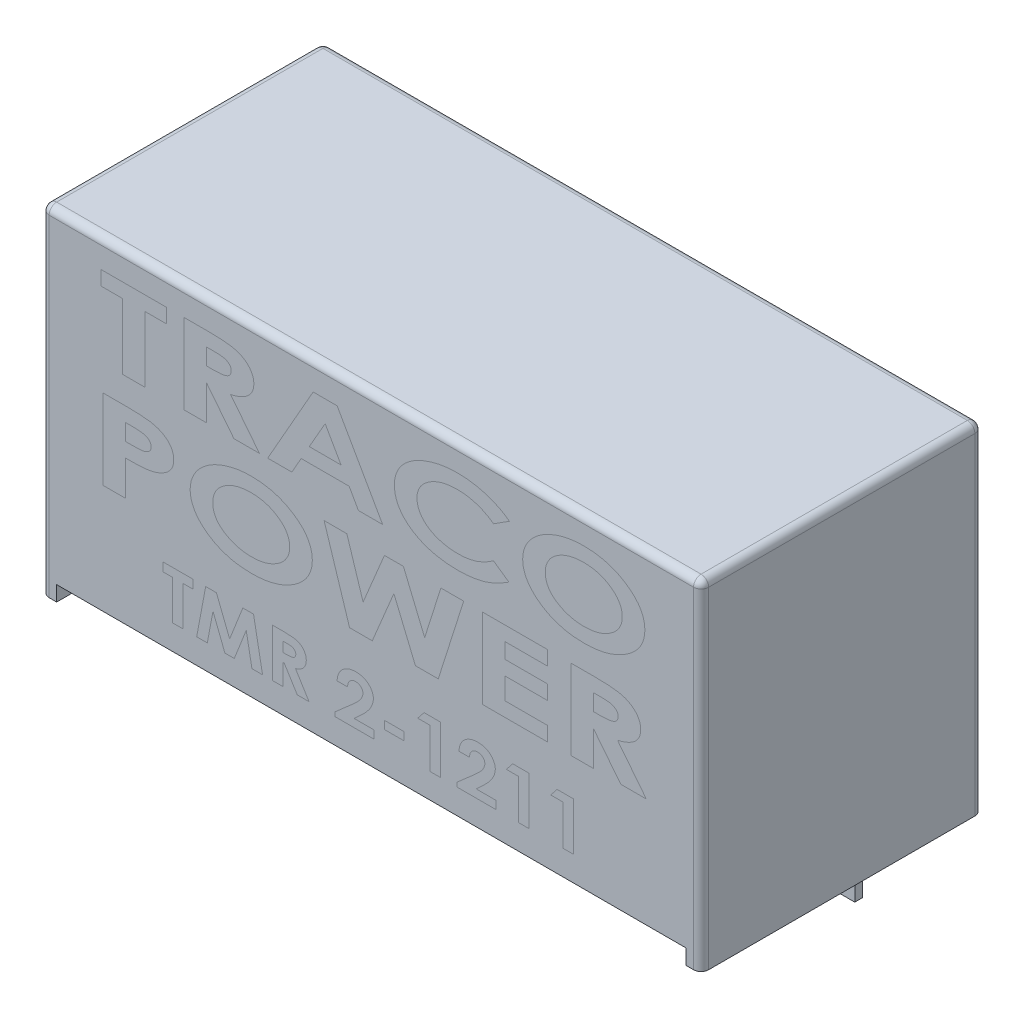
SolidWorks part; units mm, degrees
ref_plane "Plan de face" through (0, 0, 0) normal (0, 0, 1) x (1, 0, 0)
ref_plane "Plan de dessus" through (0, 0, 0) normal (0, 1, 0) x (1, 0, 0)
ref_plane "Plan de droite" through (0, 0, 0) normal (1, 0, 0) x (0, 0, -1)
sketch "Esquisse1" plane through (0, 0, 0) normal (0, 1, 0) x (1, 0, 0)
  line L1 (0, 0) -> (21.8, 0)
  line L2 (0, 0) -> (0, 9.3)
  line L3 (0, 9.3) -> (21.8, 9.3)
  line L4 (21.8, 0) -> (21.8, 9.3)
  dimension "D1" = 21.8
  dimension "D2" = 9.3
extrude "Boss.-Extru.1" add sketch "Esquisse1" along normal blind 11.2
sketch "Esquisse2" plane through (0, 0, 0) normal (0, -1, 0) x (1, 0, 0)
  line L0 (0, 0) -> (21.8, 0) construction
  line L1 (0.5, 0) -> (21.3, 0)
  line L2 (0.5, 0) -> (0.5, -9.3)
  line L3 (0.5, -9.3) -> (21.3, -9.3)
  line L4 (21.3, 0) -> (21.3, -9.3)
  line L5 (21.8, -9.3) -> (0, -9.3) construction
  line L6 (0, -9.3) -> (0, 0) construction
  line L7 (21.8, 0) -> (21.8, -9.3) construction
  line L8 (5.04, -6.6) -> (5.04, -6.85)
  line L9 (2, -6.6) -> (2.5, -6.6)
  line L10 (2, -6.6) -> (2, -6.85)
  line L11 (2, -6.85) -> (2.5, -6.85)
  line L12 (2.5, -6.6) -> (2.5, -6.85)
  line L13 (4.54, -6.85) -> (5.04, -6.85)
  line L14 (4.54, -6.6) -> (5.04, -6.6)
  line L15 (4.54, -6.6) -> (4.54, -6.85)
  line L16 (7.58, -6.6) -> (7.58, -6.85)
  line L17 (7.08, -6.85) -> (7.58, -6.85)
  line L18 (7.08, -6.6) -> (7.58, -6.6)
  line L19 (7.08, -6.6) -> (7.08, -6.85)
  line L20 (12.66, -6.6) -> (12.66, -6.85)
  line L21 (12.16, -6.85) -> (12.66, -6.85)
  line L22 (12.16, -6.6) -> (12.66, -6.6)
  line L23 (12.16, -6.6) -> (12.16, -6.85)
  line L24 (15.2, -6.6) -> (15.2, -6.85)
  line L25 (14.7, -6.85) -> (15.2, -6.85)
  line L26 (14.7, -6.6) -> (15.2, -6.6)
  line L27 (14.7, -6.6) -> (14.7, -6.85)
  line L28 (20.28, -6.6) -> (20.28, -6.85)
  line L29 (19.78, -6.85) -> (20.28, -6.85)
  line L30 (19.78, -6.6) -> (20.28, -6.6)
  line L31 (19.78, -6.6) -> (19.78, -6.85)
  line L32 (17.74, -6.6) -> (17.74, -6.85)
  line L33 (17.24, -6.85) -> (17.74, -6.85)
  line L34 (17.24, -6.6) -> (17.74, -6.6)
  line L35 (17.24, -6.6) -> (17.24, -6.85)
  dimension "D1" = 0.5
  dimension "D2" = 0.5
  dimension "D3" = 0.25
  dimension "D4" = 0.5
  dimension "D5" = 0.25
  dimension "D6" = 0.5
  dimension "D7" = 0.25
  dimension "D8" = 0.5
  dimension "D9" = 0.25
  dimension "D10" = 0.5
  dimension "D11" = 0.25
  dimension "D12" = 0.5
  dimension "D13" = 0.25
  dimension "D14" = 0.5
  dimension "D15" = 2.54
  dimension "D16" = 0.5
  dimension "D17" = 2.54
  dimension "D18" = 2.54
  dimension "D19" = 2.54
  dimension "D20" = 2.54
  dimension "D21" = 5.08
  dimension "D22" = 2
  dimension "D23" = 2.7
extrude "Enlèv. mat.-Extru.1" cut sketch "Esquisse2" against normal blind 0.5
sketch "Esquisse3" plane through (0, 0, 0) normal (0, -1, 0) x (1, 0, 0)
  line L1 (2, -6.6) -> (2.5, -6.6)
  line L2 (2, -6.6) -> (2, -6.85)
  line L3 (2, -6.85) -> (2.5, -6.85)
  line L4 (2.5, -6.6) -> (2.5, -6.85)
  line L5 (4.54, -6.6) -> (5.04, -6.6)
  line L6 (4.54, -6.6) -> (4.54, -6.85)
  line L7 (4.54, -6.85) -> (5.04, -6.85)
  line L8 (5.04, -6.6) -> (5.04, -6.85)
  line L9 (7.08, -6.6) -> (7.58, -6.6)
  line L10 (7.08, -6.6) -> (7.08, -6.85)
  line L11 (7.08, -6.85) -> (7.58, -6.85)
  line L12 (7.58, -6.6) -> (7.58, -6.85)
  line L13 (12.16, -6.6) -> (12.66, -6.6)
  line L14 (12.16, -6.6) -> (12.16, -6.85)
  line L15 (12.16, -6.85) -> (12.66, -6.85)
  line L16 (12.66, -6.6) -> (12.66, -6.85)
  line L17 (14.7, -6.6) -> (15.2, -6.6)
  line L18 (14.7, -6.6) -> (14.7, -6.85)
  line L19 (14.7, -6.85) -> (15.2, -6.85)
  line L20 (15.2, -6.6) -> (15.2, -6.85)
  line L21 (17.24, -6.6) -> (17.74, -6.6)
  line L22 (17.24, -6.6) -> (17.24, -6.85)
  line L23 (17.24, -6.85) -> (17.74, -6.85)
  line L24 (17.74, -6.6) -> (17.74, -6.85)
  line L25 (19.78, -6.6) -> (20.28, -6.6)
  line L26 (19.78, -6.6) -> (19.78, -6.85)
  line L27 (19.78, -6.85) -> (20.28, -6.85)
  line L28 (20.28, -6.6) -> (20.28, -6.85)
extrude "Boss.-Extru.3" add sketch "Esquisse3" along normal blind 2
sketch "Esquisse4" plane through (0, 0, 0) normal (0, 0, 1) x (1, 0, 0)
  text T0 "<b>TRACO</b>" font "Century Gothic" height in points 10
  text T1 "<b>POWER</b>" font "Century Gothic" height in points 10
  text T2 "<b>TMR 2-1211</b>" font "Century Gothic" height in points 6
wrap "Enroulement1" sketch "Esquisse4" wrap type scribe source sketch "Esquisse4"
fillet "Congé1" radius 0.25 8 edges at (0, 5.6, -9.3) (10.9, 11.2, -9.3) (21.8, 5.6, -9.3) (21.8, 11.2, -4.65) (21.8, 5.6, 0) (10.9, 11.2, 0) (0, 5.6, 0) (0, 11.2, -4.65)
sketch "Esquisse6" plane through (0, 0.5, 0) normal (0, -1, 0) x (1, 0, 0)
  line L0 (0.5, 0) -> (0.5, -9.3) construction
  line L1 (0.5, -0.5) -> (21.3, -0.5)
  line L2 (0.5, -0.5) -> (0.5, -8.8)
  line L3 (0.5, -8.8) -> (21.3, -8.8)
  line L4 (21.3, -0.5) -> (21.3, -8.8)
  line L5 (21.3, -9.3) -> (21.3, 0) construction
  line L6 (21.3, 0) -> (0.5, 0) construction
  line L7 (2, -6.6) -> (2.5, -6.6)
  line L8 (2, -6.6) -> (2, -6.85)
  line L9 (2, -6.85) -> (2.5, -6.85)
  line L10 (2.5, -6.6) -> (2.5, -6.85)
  line L11 (4.54, -6.6) -> (5.04, -6.6)
  line L12 (4.54, -6.6) -> (4.54, -6.85)
  line L13 (4.54, -6.85) -> (5.04, -6.85)
  line L14 (5.04, -6.6) -> (5.04, -6.85)
  line L15 (7.08, -6.6) -> (7.58, -6.6)
  line L16 (7.08, -6.6) -> (7.08, -6.85)
  line L17 (7.08, -6.85) -> (7.58, -6.85)
  line L18 (7.58, -6.6) -> (7.58, -6.85)
  line L19 (12.16, -6.6) -> (12.66, -6.6)
  line L20 (12.16, -6.6) -> (12.16, -6.85)
  line L21 (12.16, -6.85) -> (12.66, -6.85)
  line L22 (12.66, -6.6) -> (12.66, -6.85)
  line L23 (14.7, -6.6) -> (15.2, -6.6)
  line L24 (14.7, -6.6) -> (14.7, -6.85)
  line L25 (14.7, -6.85) -> (15.2, -6.85)
  line L26 (15.2, -6.6) -> (15.2, -6.85)
  line L27 (17.24, -6.6) -> (17.74, -6.6)
  line L28 (17.24, -6.6) -> (17.24, -6.85)
  line L29 (17.24, -6.85) -> (17.74, -6.85)
  line L30 (17.74, -6.6) -> (17.74, -6.85)
  line L31 (19.78, -6.6) -> (20.28, -6.6)
  line L32 (19.78, -6.6) -> (19.78, -6.85)
  line L33 (19.78, -6.85) -> (20.28, -6.85)
  line L34 (20.28, -6.6) -> (20.28, -6.85)
  line L35 (0.5, -9.3) -> (21.3, -9.3) construction
  dimension "D1" = 0.5
  dimension "D2" = 0.5
extrude "Enlèv. mat.-Extru.2" cut sketch "Esquisse6" against normal blind 0.5
fillet "Congé2" radius 0.5 32 edges at (10.9, 1, -0.5) (21.3, 1, -4.65) (10.9, 1, -8.8) (0.5, 1, -4.65) (2, 1, -6.725) (2.25, 1, -6.85) (2.5, 1, -6.725) (2.25, 1, -6.6) (4.54, 1, -6.725) (4.79, 1, -6.85) (5.04, 1, -6.725) (4.79, 1, -6.6) (7.08, 1, -6.725) (7.33, 1, -6.85) (7.58, 1, -6.725) (7.33, 1, -6.6) (12.16, 1, -6.725) (12.41, 1, -6.85) (12.66, 1, -6.725) (12.41, 1, -6.6) (14.7, 1, -6.725) (14.95, 1, -6.85) (15.2, 1, -6.725) (14.95, 1, -6.6) (17.24, 1, -6.725) (17.49, 1, -6.85) (17.74, 1, -6.725) (17.49, 1, -6.6) (19.78, 1, -6.725) (20.03, 1, -6.85) (20.28, 1, -6.725) (20.03, 1, -6.6)
